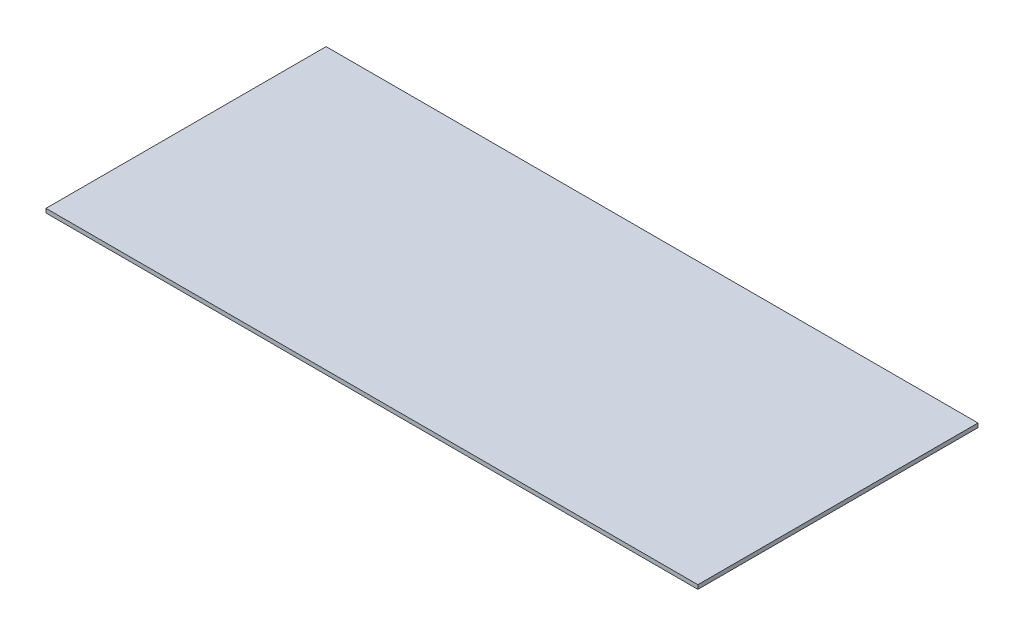
SolidWorks part; units mm, degrees
material "1060 Alloy"
ref_plane "Front" through (0, 0, 0) normal (0, 0, 1) x (1, 0, 0)
ref_plane "Top" through (0, 0, 0) normal (0, 1, 0) x (1, 0, 0)
ref_plane "Right" through (0, 0, 0) normal (1, 0, 0) x (0, 0, -1)
sketch "Sketch1" plane through (0, 0, 0) normal (0, 1, 0) x (1, 0, 0)
  line L1 (0, 0) -> (203.2, 0)
  line L2 (0, 0) -> (0, 87.3125)
  line L3 (0, 87.3125) -> (203.2, 87.3125)
  line L4 (203.2, 0) -> (203.2, 87.3125)
  dimension "D1" = 87.3125
  dimension "D2" = 203.2
extrude "Boss-Extrude1" add sketch "Sketch1" along normal blind 1.27
